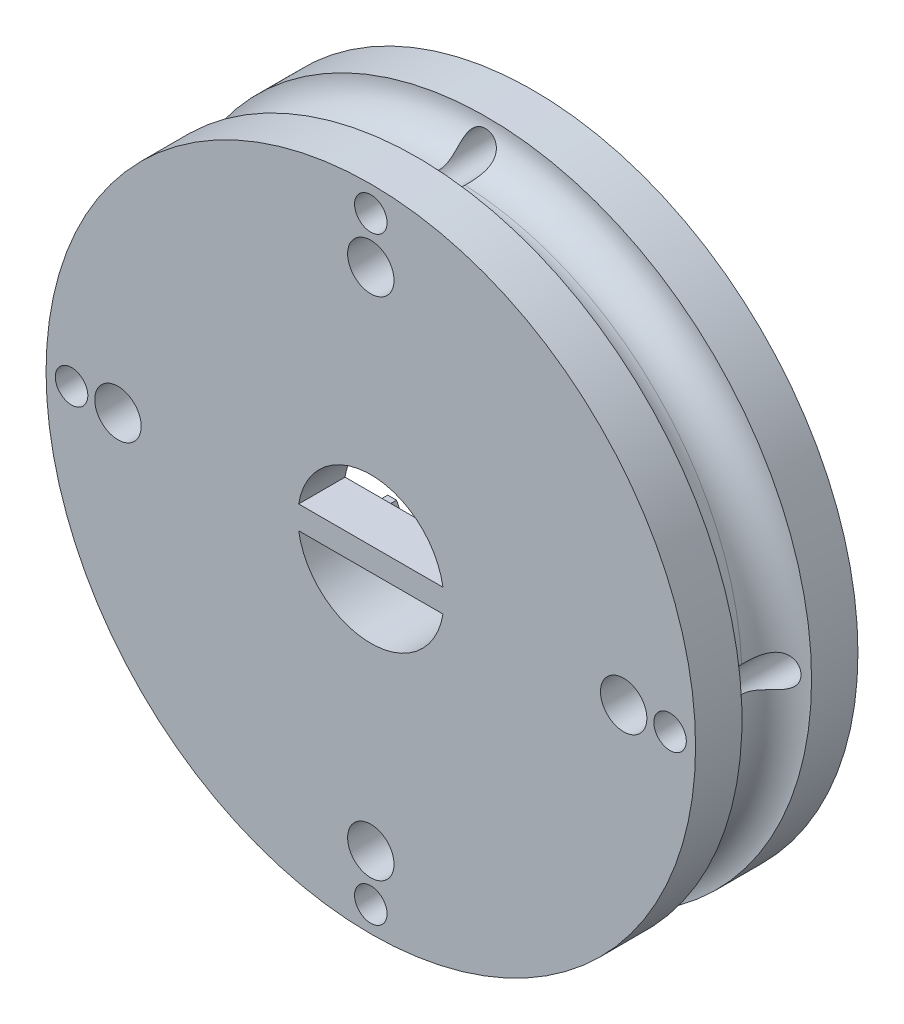
SolidWorks part; units mm, degrees
ref_plane "Front Plane" through (0, 0, 0) normal (0, 0, 1) x (1, 0, 0)
ref_plane "Top Plane" through (0, 0, 0) normal (0, 1, 0) x (1, 0, 0)
ref_plane "Right Plane" through (0, 0, 0) normal (1, 0, 0) x (0, 0, -1)
sketch "Sketch1" plane through (0, 0, 0) normal (0, 0, 1) x (1, 0, 0)
  circle A0 centre (0, 0) radius 14
extrude "Boss-Extrude1" add sketch "Sketch1" along normal blind 7
sketch "Sketch3" plane through (0, 0, 0) normal (0, 0, -1) x (-1, 0, 0)
  circle A0 centre (0, 0) radius 3.15
extrude "Cut-Extrude1" cut sketch "Sketch3" against normal through all
sketch "Sketch4" plane through (0, 0, 7) normal (0, 0, 1) x (1, 0, 0)
  line L1 (-3.5, 0.5) -> (3.5, 0.5)
  line L2 (-3.5, 0.5) -> (-3.5, -0.5)
  line L3 (-3.5, -0.5) -> (3.5, -0.5)
  line L4 (3.5, 0.5) -> (3.5, -0.5)
  dimension "D1" = 7
  dimension "D2" = 1
  dimension "D3" = 0.5
  dimension "D4" = 3.5
extrude "Boss-Extrude2" add sketch "Sketch4" against normal blind 2
sketch "Sketch5" plane through (0, 0, 0) normal (0, 0, -1) x (-1, 0, 0)
  circle A0 centre (0, 0) radius 3.5
  circle A1 centre (0, 0) radius 12
extrude "Cut-Extrude2" cut sketch "Sketch5" against normal blind 5
sketch "Sketch6" plane through (0, 0, 0) normal (0, 0, -1) x (-1, 0, 0)
  line L1 (-3.5, 1.25) -> (3.5, 1.25)
  line L2 (-3.5, 1.25) -> (-3.5, -1.25)
  line L3 (-3.5, -1.25) -> (3.5, -1.25)
  line L4 (3.5, 1.25) -> (3.5, -1.25)
  dimension "D1" = 1.25
  dimension "D2" = 3.5
extrude "Cut-Extrude3" cut sketch "Sketch6" against normal blind 5
sketch "Sketch7" plane through (0, 0, 0) normal (0, 0, -1) x (-1, 0, 0)
  circle A0 centre (0, 0) radius 14
  circle A1 centre (0, 0) radius 12.5
extrude "Cut-Extrude4" cut sketch "Sketch7" against normal blind 5
sketch "Sketch8" plane through (0, 0, 0) normal (0, 0, 1) x (1, 0, 0)
  circle A0 centre (0, 0) radius 14
  circle A1 centre (0, 0) radius 12.5
extrude "Boss-Extrude3" add sketch "Sketch8" along normal blind 2
fillet "Fillet1" radius 1.5 2 edges at (-12.5, 0, 5) (12.5, 0, 2)
sketch "Sketch9" plane through (0, 0, 0) normal (0, 0, -1) x (-1, 0, 0)
  circle A0 centre (-12.9, 0) radius 0.7
  circle A1 centre (12.9, 0) radius 0.7
  circle A2 centre (0, 12.9) radius 0.7
  circle A3 centre (0, -12.9) radius 0.7
  circle A4 centre (-10.9, 0) radius 1
  circle A5 centre (0, 10.9) radius 1
  circle A6 centre (0, -10.9) radius 1
  circle A7 centre (10.9, 0) radius 1
  point P13 (0.2388, 8.8241)
  point P16 (0.2388, -8.7511)
  point P19 (7.2297, -1.9019)
  point P20 (10.3925, 0)
  point P21 (0, -9.2141)
  point P22 (-9.7076, 0)
  point P23 (0, 8.7864)
  dimension "D1" = 12.9
  dimension "D2" = 12.9
  dimension "D5" = 2
  dimension "D3" = 12.9
  dimension "D4" = 12.9
  dimension "D6" = 2
  dimension "D7" = 2
  dimension "D8" = 2
extrude "Cut-Extrude7" cut sketch "Sketch9" against normal through all both and the other way through all contours A5 | A2 | A1 | A3 | A0 | A4 | A7 | A6 region at (0, 10.9, 0)
sketch "Sketch10" plane through (0, 0, 0) normal (0, 0, -1) x (-1, 0, 0)
  line L1 (-3.4287, 3.6232) -> (3.4457, 3.6232)
  line L2 (-3.4287, 3.6232) -> (-3.4287, -3.9227)
  line L3 (-3.4287, -3.9227) -> (3.4457, -3.9227)
  line L4 (3.4457, 3.6232) -> (3.4457, -3.9227)
extrude "Cut-Extrude8" cut sketch "Sketch10" against normal blind 3
